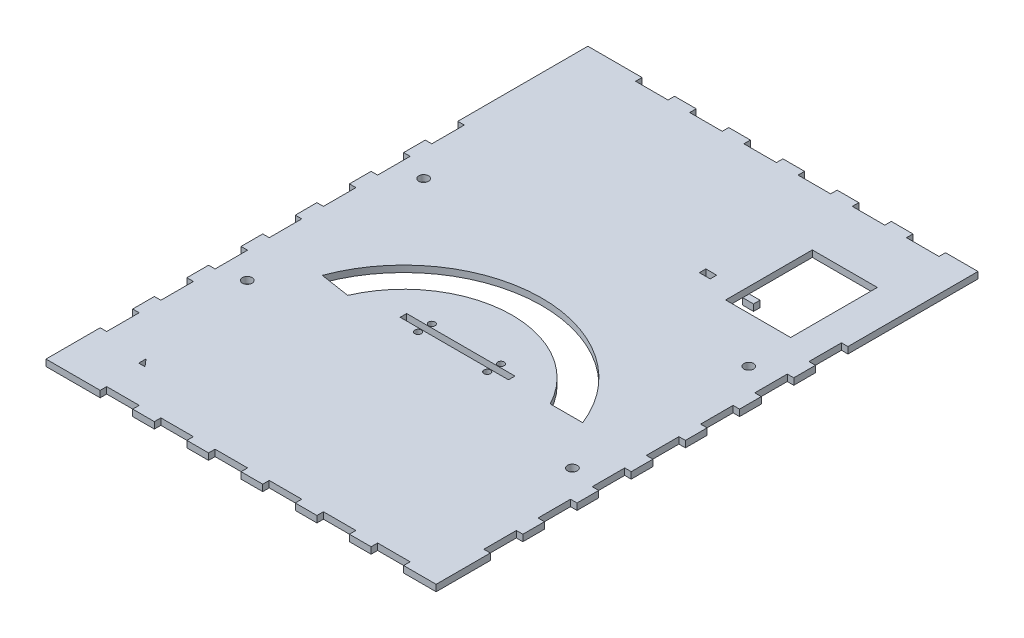
SolidWorks part; units mm, degrees
ref_plane "Front Plane" through (0, 0, 0) normal (0, 0, 1) x (1, 0, 0)
ref_plane "Top Plane" through (0, 0, 0) normal (0, 1, 0) x (1, 0, 0)
ref_plane "Right Plane" through (0, 0, 0) normal (1, 0, 0) x (0, 0, -1)
sketch "Sketch1" plane through (0, 0, 0) normal (0, 1, 0) x (1, 0, 0)
  line L0 (-90.3569, -190.1013) -> (-87.3569, -190.1013)
  line L1 (89.6431, -215.1013) -> (-90.3569, -215.1013)
  line L2 (89.6431, -215.1013) -> (89.6431, 34.8987)
  line L3 (89.6431, 34.8987) -> (-90.3569, 34.8987)
  line L4 (-90.3569, -215.1013) -> (-90.3569, 34.8987)
  line L5 (-87.3569, -190.1013) -> (-87.3569, -175.1013)
  line L6 (-87.3569, -175.1013) -> (-90.3569, -175.1013)
  line L7 (-87.3569, -150.1013) -> (-90.3569, -150.1013)
  line L8 (-87.3569, -165.1013) -> (-87.3569, -150.1013)
  line L9 (-90.3569, -165.1013) -> (-87.3569, -165.1013)
  line L10 (-87.3569, -125.1013) -> (-90.3569, -125.1013)
  line L11 (-87.3569, -140.1013) -> (-87.3569, -125.1013)
  line L12 (-90.3569, -140.1013) -> (-87.3569, -140.1013)
  line L13 (-87.3569, -100.1013) -> (-90.3569, -100.1013)
  line L14 (-87.3569, -115.1013) -> (-87.3569, -100.1013)
  line L15 (-90.3569, -115.1013) -> (-87.3569, -115.1013)
  line L16 (-87.3569, -75.1013) -> (-90.3569, -75.1013)
  line L17 (-87.3569, -90.1013) -> (-87.3569, -75.1013)
  line L18 (-90.3569, -90.1013) -> (-87.3569, -90.1013)
  line L19 (-87.3569, -50.1013) -> (-90.3569, -50.1013)
  line L20 (-87.3569, -65.1013) -> (-87.3569, -50.1013)
  line L21 (-90.3569, -65.1013) -> (-87.3569, -65.1013)
  line L22 (-87.3569, -25.1013) -> (-90.3569, -25.1013)
  line L23 (-87.3569, -40.1013) -> (-87.3569, -25.1013)
  line L24 (-90.3569, -40.1013) -> (-87.3569, -40.1013)
  line L25 (-65.3569, -215.1013) -> (-65.3569, -212.1013)
  line L26 (-65.3569, -212.1013) -> (-50.3569, -212.1013)
  line L27 (-50.3569, -212.1013) -> (-50.3569, -215.1013)
  line L28 (-40.3569, -212.1013) -> (-25.3569, -212.1013)
  line L29 (-25.3569, -212.1013) -> (-25.3569, -215.1013)
  line L30 (-40.3569, -215.1013) -> (-40.3569, -212.1013)
  line L31 (-15.3569, -212.1013) -> (-0.3569, -212.1013)
  line L32 (-0.3569, -212.1013) -> (-0.3569, -215.1013)
  line L33 (-15.3569, -215.1013) -> (-15.3569, -212.1013)
  line L34 (9.6431, -212.1013) -> (24.6431, -212.1013)
  line L35 (24.6431, -212.1013) -> (24.6431, -215.1013)
  line L36 (9.6431, -215.1013) -> (9.6431, -212.1013)
  line L37 (34.6431, -212.1013) -> (49.6431, -212.1013)
  line L38 (49.6431, -212.1013) -> (49.6431, -215.1013)
  line L39 (34.6431, -215.1013) -> (34.6431, -212.1013)
  line L40 (59.6431, -212.1013) -> (74.6431, -212.1013)
  line L41 (74.6431, -212.1013) -> (74.6431, -215.1013)
  line L42 (59.6431, -215.1013) -> (59.6431, -212.1013)
  line L43 (89.6431, -90.1013) -> (-90.3569, -90.1013) construction
  line L45 (-0.3569, 34.8987) -> (-0.3569, -215.1013) construction
  line L46 (89.6431, -40.1013) -> (86.6431, -40.1013)
  line L47 (86.6431, -40.1013) -> (86.6431, -25.1013)
  line L48 (86.6431, -25.1013) -> (89.6431, -25.1013)
  line L49 (89.6431, -65.1013) -> (86.6431, -65.1013)
  line L50 (86.6431, -65.1013) -> (86.6431, -50.1013)
  line L51 (86.6431, -50.1013) -> (89.6431, -50.1013)
  line L52 (89.6431, -90.1013) -> (86.6431, -90.1013)
  line L53 (86.6431, -90.1013) -> (86.6431, -75.1013)
  line L54 (86.6431, -75.1013) -> (89.6431, -75.1013)
  line L55 (89.6431, -115.1013) -> (86.6431, -115.1013)
  line L56 (86.6431, -115.1013) -> (86.6431, -100.1013)
  line L57 (86.6431, -100.1013) -> (89.6431, -100.1013)
  line L58 (89.6431, -140.1013) -> (86.6431, -140.1013)
  line L59 (86.6431, -140.1013) -> (86.6431, -125.1013)
  line L60 (86.6431, -125.1013) -> (89.6431, -125.1013)
  line L61 (89.6431, -165.1013) -> (86.6431, -165.1013)
  line L62 (86.6431, -165.1013) -> (86.6431, -150.1013)
  line L63 (86.6431, -150.1013) -> (89.6431, -150.1013)
  line L64 (86.6431, -175.1013) -> (89.6431, -175.1013)
  line L65 (86.6431, -190.1013) -> (86.6431, -175.1013)
  line L66 (89.6431, -190.1013) -> (86.6431, -190.1013)
  line L67 (59.6431, 34.8987) -> (59.6431, 31.8987)
  line L68 (74.6431, 31.8987) -> (74.6431, 34.8987)
  line L69 (59.6431, 31.8987) -> (74.6431, 31.8987)
  line L70 (34.6431, 34.8987) -> (34.6431, 31.8987)
  line L71 (49.6431, 31.8987) -> (49.6431, 34.8987)
  line L72 (34.6431, 31.8987) -> (49.6431, 31.8987)
  line L73 (9.6431, 34.8987) -> (9.6431, 31.8987)
  line L74 (24.6431, 31.8987) -> (24.6431, 34.8987)
  line L75 (9.6431, 31.8987) -> (24.6431, 31.8987)
  line L76 (-15.3569, 34.8987) -> (-15.3569, 31.8987)
  line L77 (-0.3569, 31.8987) -> (-0.3569, 34.8987)
  line L78 (-15.3569, 31.8987) -> (-0.3569, 31.8987)
  line L79 (-40.3569, 34.8987) -> (-40.3569, 31.8987)
  line L80 (-25.3569, 31.8987) -> (-25.3569, 34.8987)
  line L81 (-40.3569, 31.8987) -> (-25.3569, 31.8987)
  line L82 (-50.3569, 31.8987) -> (-50.3569, 34.8987)
  line L83 (-65.3569, 31.8987) -> (-50.3569, 31.8987)
  line L84 (-65.3569, 34.8987) -> (-65.3569, 31.8987)
  line L85 (89.6431, 34.8987) -> (-90.3569, 34.8987)
  dimension "D1" = 180
  dimension "D2" = 250
  dimension "D3" = 3
  dimension "D4" = 15
  dimension "D5" = 25
  dimension "D7" = 15
  dimension "D8" = 3
  dimension "D9" = 180
  dimension "D10" = 250
  dimension "D11" = 25
  dimension "D6" = 7
  dimension "D12" = 6
extrude "Boss-Extrude1" add sketch "Sketch1" along normal blind 3 contours L84 L3 L4 L22 L23 L24 L19 L20 L21 L16 L17 L18 L13 L14 L15 L10 L11 L12 L7 L8 L9 L6 L5 L0 L1 L25 L26 L27 L30 L28 L29 L33 L31 L32 L36 L34 L35 L39 L37 L38 region at (-0.4185, 0, 89.8498)
sketch "Sketch2" plane through (0, 3, 0) normal (0, 1, 0) x (1, 0, 0)
  line L0 (-67.3492, -195.3249) -> (-64.4505, -195.3249)
  line L1 (-64.4505, -195.3249) -> (-67.3492, -191.9802)
  line L2 (-67.3492, -191.9802) -> (-67.3492, -195.3249)
extrude "Cut-Extrude1" cut sketch "Sketch2" against normal blind 10
sketch "Sketch3" plane through (0, 3, 0) normal (0, 1, 0) x (1, 0, 0)
  line L0 (-0.3569, 34.8987) -> (-0.3569, -215.1013) construction
  line L1 (58.8954, -116.7202) -> (43.8954, -116.7202)
  line L2 (-25.3569, -116.7123) -> (24.6431, -116.7123)
  line L3 (-25.3569, -116.7123) -> (-25.3569, -113.7123)
  line L4 (-25.3569, -113.7123) -> (24.6431, -113.7123)
  line L5 (24.6431, -116.7123) -> (24.6431, -113.7123)
  line L6 (-25.3569, -116.7123) -> (24.6431, -113.7123) construction
  line L7 (-25.3569, -113.7123) -> (24.6431, -116.7123) construction
  line L8 (-46.2106, -120.0541) -> (-60.0642, -117.9115)
  line L9 (25.8444, -29.866) -> (30.8444, -29.866)
  line L10 (72.813, -34.7147) -> (42.813, -34.7147)
  line L11 (-90.3569, -75.1013) -> (-90.3569, -65.1013) construction
  line L12 (72.813, -34.7147) -> (72.813, 5.2853)
  line L13 (72.813, 5.2853) -> (42.813, 5.2853)
  line L14 (42.813, -34.7147) -> (42.813, 5.2853)
  line L15 (72.813, -34.7147) -> (42.813, 5.2853) construction
  line L16 (72.813, 5.2853) -> (42.813, -34.7147) construction
  line L17 (45.8444, -29.866) -> (50.8444, -29.866)
  line L18 (45.8444, -29.866) -> (45.8444, -26.866)
  line L19 (45.8444, -26.866) -> (50.8444, -26.866)
  line L20 (50.8444, -29.866) -> (50.8444, -26.866)
  line L21 (25.8444, -29.866) -> (25.8444, -26.866)
  line L22 (25.8444, -26.866) -> (30.8444, -26.866)
  line L23 (30.8444, -29.866) -> (30.8444, -26.866)
  arc A0 (58.8954, -116.7202) -> (-60.0642, -117.9115) centre (-0.3569, -140.0262) ccw
  arc A1 (43.8954, -116.7202) -> (-46.2106, -120.0541) centre (-0.3569, -140.0262) ccw
  circle A2 centre (16.5283, -118.41) radius 1.5
  circle A3 centre (-15.3904, -118.41) radius 1.5
  circle A4 centre (-15.3904, -112.0528) radius 1.5
  circle A5 centre (16.5283, -112.0528) radius 1.5
  circle A6 centre (-75.3569, -55.8617) radius 2.25
  circle A7 centre (-75.3569, -137.2386) radius 2.25
  circle A8 centre (74.6431, -137.2386) radius 2.25
  circle A9 centre (74.6431, -55.8617) radius 2.25
  point P4 (-0.3569, -115.2123)
  point P16 (57.813, -14.7147)
  dimension "D4" = 63.6711
  dimension "D5" = 3
  dimension "D6" = 4.5
  dimension "D1" = 3
  dimension "D2" = 50
  dimension "D3" = 15
  dimension "D7" = 15
  dimension "D8" = 30
  dimension "D9" = 40
  dimension "D10" = 3
  dimension "D11" = 5
  dimension "D12" = 15
  dimension "D13" = 5
extrude "Cut-Extrude8" cut sketch "Sketch3" against normal blind 9
